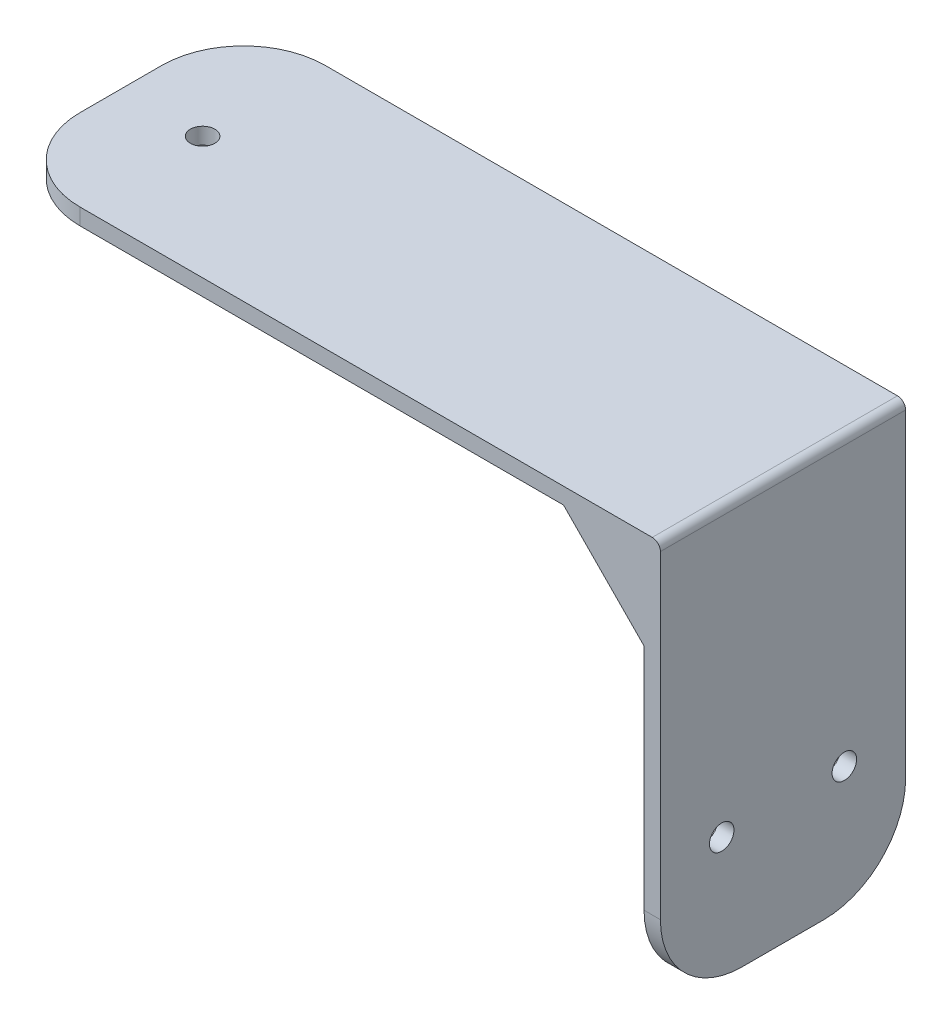
SolidWorks part; units mm, degrees
ref_plane "Front Plane" through (0, 0, 0) normal (0, 0, 1) x (1, 0, 0)
ref_plane "Top Plane" through (0, 0, 0) normal (0, 1, 0) x (1, 0, 0)
ref_plane "Right Plane" through (0, 0, 0) normal (1, 0, 0) x (0, 0, -1)
sketch "Sketch1" plane through (0, 0, 0) normal (0, 1, 0) x (1, 0, 0)
  line L1 (0, 0) -> (80, 0)
  line L2 (0, 0) -> (0, 30)
  line L3 (0, 30) -> (80, 30)
  line L4 (80, 0) -> (80, 30)
  circle A0 centre (10, 15) radius 1.5
  dimension "D3" = 10
  dimension "D4" = 15
  dimension "D1" = 30
  dimension "D2" = 80
extrude "Boss-Extrude1" add sketch "Sketch1" along normal blind 2
sketch "Sketch2" plane through (0, 2, 0) normal (0, 1, 0) x (1, 0, 0)
  line L0 (80, 30) -> (0, 30) construction
  line L1 (80, 0) -> (79, 0)
  line L2 (80, 0) -> (80, 30)
  line L3 (80, 30) -> (79, 30)
  line L4 (79, 0) -> (79, 30)
  line L6 (80, 0) -> (81, 0)
  line L7 (80, 0) -> (80, 30)
  line L8 (80, 30) -> (81, 30)
  line L9 (81, 0) -> (81, 30)
  line M2 (0, 0) -> (80, 0)
  line M3 (80, 0) -> (80, 30)
  line M4 (80, 30) -> (0, 30)
  dimension "D1" = 1
  dimension "D2" = 1
extrude "Boss-Extrude2" add sketch "Sketch2" against normal blind 50 contours L4 M2 M3 M4 | L6 L9 L8 M3 region at (79.5, 2, -15) region at (80.5, 2, -15)
sketch "Sketch3" plane through (79, 0, 0) normal (-1, 0, 0) x (0, 0, 1)
  line L0 (-30, -48) -> (-30, 0) construction
  line L1 (0, -48) -> (-30, -48) construction
  line L2 (0, -48) -> (0, 0) construction
  circle A0 centre (-22.5, -33) radius 1.5
  circle A1 centre (-7.5, -33) radius 1.5
  dimension "D1" = 3
  dimension "D2" = 3
  dimension "D3" = 7.5
  dimension "D4" = 15
  dimension "D5" = 7.5
  dimension "D6" = 15
extrude "Cut-Extrude1" cut sketch "Sketch3" against normal blind 70
fillet "Fillet1" radius 1 2 edges at (79, 0, -15) (81, 2, -15)
fillet "Fillet2" radius 10 4 edges at (80, -48, 0) (80, -48, -30) (0, 1, 0) (0, 1, -30)
ref_plane "Plane1" through (0, 0, -15) normal (0, 0, 1) x (1, 0, 0)
sketch "Sketch4" plane through (0, 0, 0) normal (0, 0, 1) x (1, 0, 0)
  line L0 (10, 0) -> (78, 0) construction
  line L1 (69, 0) -> (79, 0)
  line L2 (69, 0) -> (69, -10)
  line L3 (69, -10) -> (79, -10)
  line L4 (79, 0) -> (79, -10)
  line L5 (79, -38) -> (79, -1) construction
  line L6 (69.1511, 0) -> (79, -10)
  circle A0 centre (78, -1) radius 1
  dimension "D1" = 10
  dimension "D2" = 10
extrude "Boss-Extrude3" add sketch "Sketch4" against normal blind 2 contours A0 L1 L6 L4 | A0 region at (75.5464, -3.5076, 0) region at (78, -1, 0)
mirror "Mirror1" about plane through (0, 0, -15) normal (0, 0, 1) of "Boss-Extrude3"
